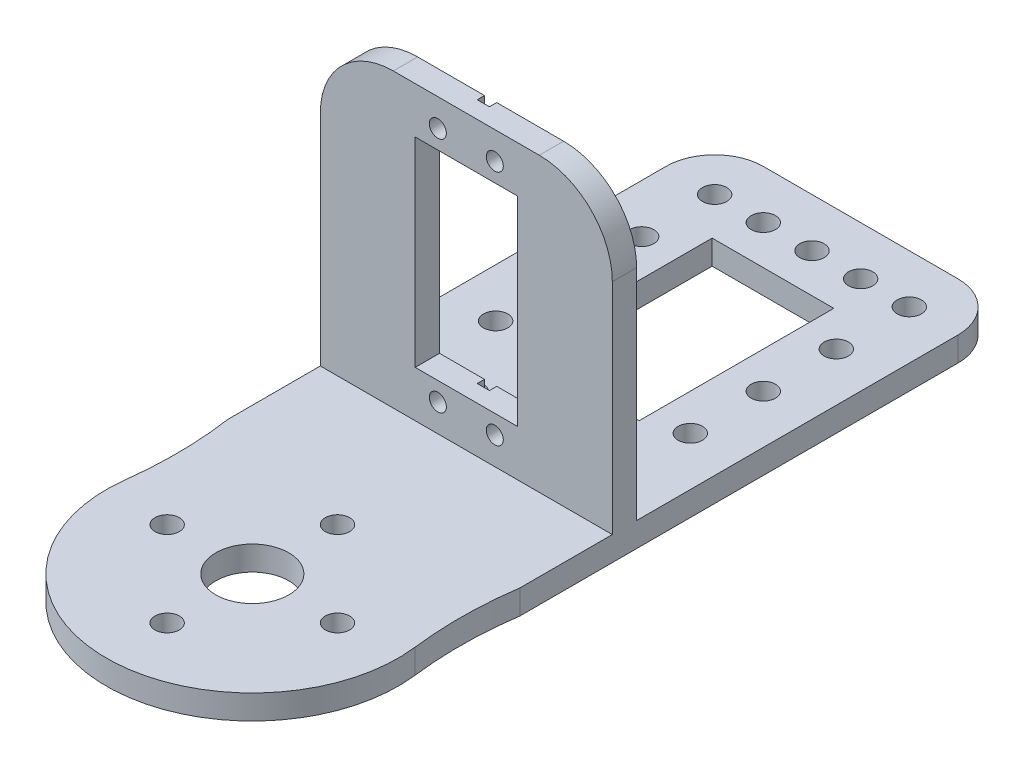
SolidWorks part; units mm, degrees
note: '?' marks a value the reader was unsure of.
ref_plane "Front Plane" through (0, 0, 0) normal (0, 0, 1) x (1, 0, 0)
ref_plane "Top Plane" through (0, 0, 0) normal (0, 1, 0) x (1, 0, 0)
ref_plane "Right Plane" through (0, 0, 0) normal (1, 0, 0) x (0, 0, -1)
sketch "Sketch1" plane through (0, 0, 0) normal (0, 1, 0) x (1, 0, 0)
  line L1 (-30, -50) -> (30, -50)
  line L2 (-30, -50) -> (-30, 50)
  line L3 (-30, 50) -> (30, 50)
  line L4 (30, -50) -> (30, 50)
  line L5 (-30, -50) -> (30, 50) construction
  line L6 (-30, 50) -> (30, -50) construction
  point P0 (0, 0)
  dimension "D1" = 60
  dimension "D2" = 100
extrude "Boss-Extrude1" add sketch "Sketch1" along normal blind 5
sketch "Sketch2" plane through (0, 5, 0) normal (0, 1, 0) x (1, 0, 0)
  line L0 (0, 0) -> (0, 40) construction
  line L1 (0, 0) -> (14.3646, 0) construction
  circle A0 centre (0, 40) radius 2.5
  circle A1 centre (10, 40) radius 2.5
  circle A2 centre (20, 40) radius 2.5
  circle A3 centre (-20, 40) radius 2.5
  circle A4 centre (-10, 40) radius 2.5
  dimension "D1" = 5
  dimension "D2" = 40
  dimension "D4" = 10
  dimension "D3" = 3
extrude "Cut-Extrude1" cut sketch "Sketch2" against normal blind 5
sketch "Sketch5" plane through (0, 5, 0) normal (0, 1, 0) x (1, 0, 0)
  line L0 (0, 0) -> (0, -75) construction
  line L1 (-30, -50) -> (30, -50)
  circle A4 centre (0, -75) radius 30
  arc A5 (30, -50) -> (29.7733, -71.3189) centre (109.1688, -61.5025) ccw
  arc A6 (-30, -50) -> (-29.7733, -71.3189) centre (-109.1688, -61.5025) cw
  dimension "D1" = 60
  dimension "D2" = 80
  dimension "D3" = 75
extrude "Boss-Extrude2" add sketch "Sketch5" against normal blind 5
sketch "Sketch6" plane through (0, 5, 0) normal (0, 1, 0) x (1, 0, 0)
  circle A0 centre (0, -75) radius 7.5
  dimension "D1" = 15
extrude "Cut-Extrude3" cut sketch "Sketch6" against normal blind 5
sketch "Sketch7" plane through (0, 5, 0) normal (0, 1, 0) x (1, 0, 0)
  line L0 (0, 0) -> (0, -28.53) construction
  line L6 (30, -50) -> (30, 50) construction
  line L7 (-30, -31.03) -> (30, -31.03)
  line L10 (-30, -31.03) -> (-30, -26.03)
  line L11 (-30, -26.03) -> (30, -26.03)
  line L12 (30, -31.03) -> (30, -26.03)
  line L13 (-30, -31.03) -> (30, -26.03) construction
  line L15 (-30, -26.03) -> (30, -31.03) construction
  dimension "D2" = 28.53
  dimension "D1" = 5
extrude "Boss-Extrude3" add sketch "Sketch7" along normal blind 60
sketch "Sketch8" plane through (0, 0, 31.03) normal (0, 0, 1) x (1, 0, 0)
  line L0 (0, 0) -> (0, 35) construction
  line L1 (0, 35) -> (0, 59.35) construction
  line L2 (-10.5, 14.5) -> (10.5, 14.5)
  line L3 (-10.5, 14.5) -> (-10.5, 55.5)
  line L4 (-10.5, 55.5) -> (10.5, 55.5)
  line L16 (10.5, 14.5) -> (10.5, 55.5)
  line L18 (-10.5, 14.5) -> (10.5, 55.5) construction
  line L19 (-10.5, 55.5) -> (10.5, 14.5) construction
  line L20 (0, 59.35) -> (-5.85, 59.35) construction
  line L21 (0, 35) -> (10.5, 35) construction
  circle A14 centre (-5.85, 59.35) radius 1.75
  circle A15 centre (5.85, 59.35) radius 1.75
  circle A16 centre (5.85, 10.65) radius 1.75
  circle A17 centre (-5.85, 10.65) radius 1.75
  dimension "D5" = 3.5
  dimension "D3" = 5.85
  dimension "D1" = 21
  dimension "D2" = 41
  dimension "D4" = 24.35
  dimension "D6" = 35
sketch "Sketch9" plane through (0, 5, 0) normal (0, 1, 0) x (1, 0, 0)
  line L0 (0, 0) -> (0, -7.5) construction
  line L1 (30, -50) -> (30, -31.03) construction
  line L2 (-30, -10) -> (30, -10)
  line L3 (-30, -10) -> (-30, -5)
  line L4 (-30, -5) -> (30, -5)
  line L5 (30, -10) -> (30, -5)
  line L6 (-30, -10) -> (30, -5) construction
  line L7 (-30, -5) -> (30, -10) construction
  dimension "D1" = 5
  dimension "D2" = 7.5
extrude "Boss-Extrude4" [suppressed] add sketch "Sketch9" along normal blind 30
ref_axis "Axis1" through (0, 0, 75) along (0, 1, 0)?
extrude "Cut-Extrude5" cut sketch "Sketch8" against normal blind 30
fillet "Fillet1" radius 15 2 edges at (30, 65, 28.53) (-30, 65, 28.53)
sketch "Sketch13" plane through (0, 5, 0) normal (0, 1, 0) x (1, 0, 0)
  line L0 (-20, 40) -> (-20, 25) construction
  line L1 (0, 0) -> (0, 25.3062) construction
  circle A0 centre (-20, 25) radius 2.5
  circle A1 centre (-20, 10) radius 2.5
  circle A2 centre (-20, -5) radius 2.5
  circle A3 centre (20, -5) radius 2.5
  circle A4 centre (20, 10) radius 2.5
  circle A5 centre (20, 25) radius 2.5
  dimension "D2" = 5
  dimension "D1" = 15
  dimension "D4" = 15
  dimension "D3" = 3
extrude "Cut-Extrude7" cut sketch "Sketch13" against normal blind 10
sketch "Sketch15" plane through (0, 5, 0) normal (0, 1, 0) x (1, 0, 0)
  line L0 (-20, -5) -> (-20, -20) construction
  line L1 (-20, -20) -> (-9.8126, -20) construction
  circle A0 centre (-20, -20) radius 2.5
  circle A1 centre (-10, -20) radius 2.5
  circle A2 centre (0, -20) radius 2.5
  circle A3 centre (10, -20) radius 2.5
  circle A4 centre (20, -20) radius 2.5
  dimension "D1" = 5
  dimension "D2" = 15
  dimension "D4" = 10
  dimension "D3" = 5
extrude "Cut-Extrude8" cut sketch "Sketch15" against normal blind 10
sketch "Sketch16" plane through (0, 5, 0) normal (0, 1, 0) x (1, 0, 0)
  line L0 (-30, 11.985) -> (30, 11.985) construction
  line L1 (-30, 50) -> (-30, -26.03) construction
  line L2 (30, -26.03) -> (30, 50) construction
  line L3 (30, 11.985) -> (0, 11.985) construction
  line L5 (-12.5, -8.015) -> (12.5, -8.015)
  line L6 (-12.5, -8.015) -> (-12.5, 31.985)
  line L7 (-12.5, 31.985) -> (12.5, 31.985)
  line L8 (12.5, -8.015) -> (12.5, 31.985)
  line L9 (-12.5, -8.015) -> (12.5, 31.985) construction
  line L10 (-12.5, 31.985) -> (12.5, -8.015) construction
  dimension "D1" = 40
  dimension "D2" = 25
extrude "Cut-Extrude9" cut sketch "Sketch16" against normal blind 10
fillet "Fillet3" radius 10 2 edges at (30, 2.5, -50) (-30, 2.5, -50)
sketch "Sketch17" plane through (0, 5, 0) normal (0, 1, 0) x (1, 0, 0)
  circle A0 centre (0, -75) radius 17.5 construction
  circle A1 centre (0, -57.5) radius 2.5
  circle A2 centre (17.5, -75) radius 2.5
  circle A3 centre (0, -92.5) radius 2.5
  circle A4 centre (-17.5, -75) radius 2.5
  point P14 (0, -75)
  dimension "D1" = 35
  dimension "D2" = 5
  dimension "D3" = 4
extrude "Cut-Extrude10" cut sketch "Sketch17" against normal blind 10
sketch "Sketch18" plane through (0, 0, 26.03) normal (0, 0, -1) x (-1, 0, 0)
  line L0 (-10.5, 35) -> (10.5, 35) construction
  line L1 (-10.5, 14.5) -> (-10.5, 55.5) construction
  line L2 (10.5, 55.5) -> (10.5, 14.5) construction
  line L3 (10.5, 35) -> (0, 35) construction
  line L4 (0, 35) -> (0, 60) construction
  line L5 (-15, 65) -> (15, 65) construction
  line L6 (-1.25, 55) -> (1.25, 55)
  line L7 (-1.25, 55) -> (-1.25, 65)
  line L8 (-1.25, 65) -> (1.25, 65)
  line L9 (1.25, 55) -> (1.25, 65)
  line L10 (-1.25, 55) -> (1.25, 65) construction
  line L11 (-1.25, 65) -> (1.25, 55) construction
  line L12 (-1.25, 5) -> (1.25, 15) construction
  line L13 (-1.25, 15) -> (1.25, 5) construction
  line L14 (1.25, 15) -> (1.25, 5)
  line L15 (-1.25, 5) -> (1.25, 5)
  line L16 (-1.25, 15) -> (-1.25, 5)
  line L17 (-1.25, 15) -> (1.25, 15)
  dimension "D1" = 2.5
  dimension "D2" = 10
extrude "Cut-Extrude11" cut sketch "Sketch18" against normal blind 1.5
